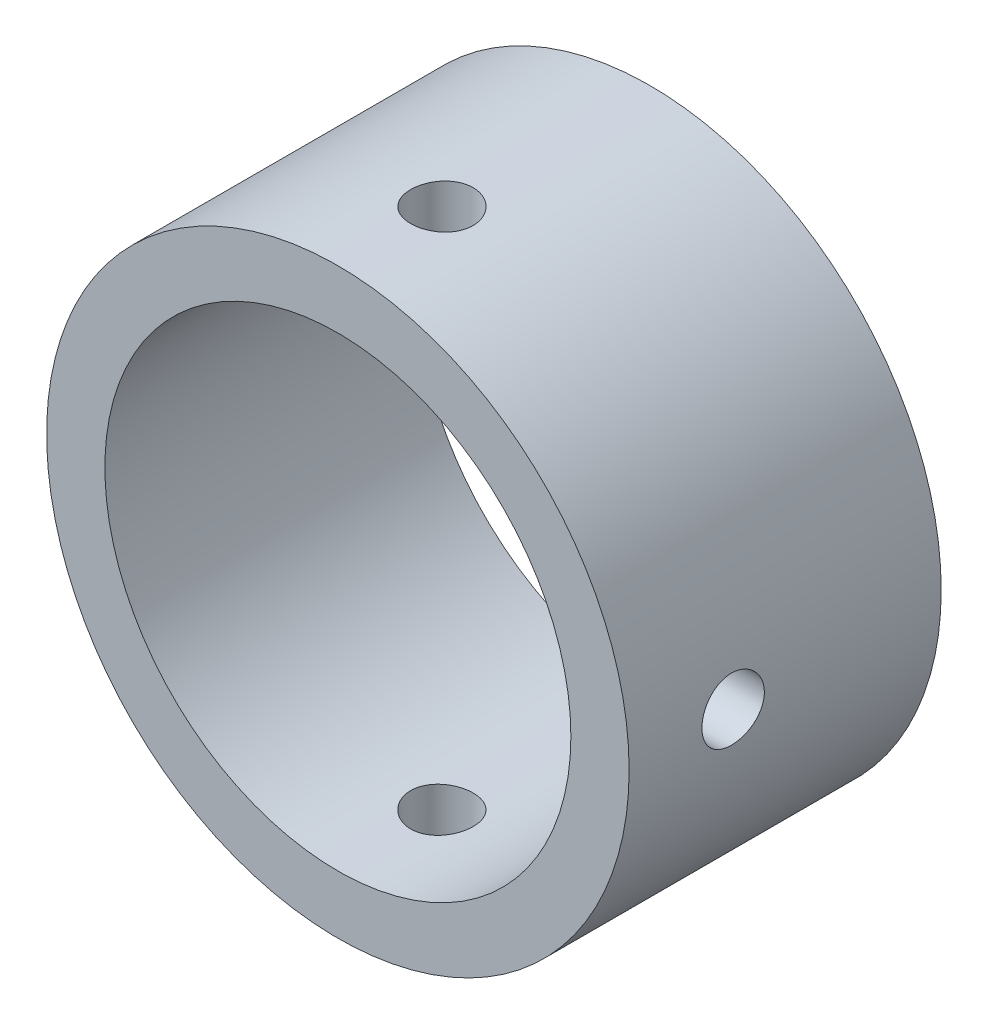
SolidWorks part; units mm, degrees
ref_plane "Front Plane" through (0, 0, 0) normal (0, 0, 1) x (1, 0, 0)
ref_plane "Top Plane" through (0, 0, 0) normal (0, 1, 0) x (1, 0, 0)
ref_plane "Right Plane" through (0, 0, 0) normal (1, 0, 0) x (0, 0, -1)
ref_axis "Z" through (0, 0, 5.75) along (0, 0, -1)
ref_axis "X" through (17.0818, 0, 0) along (-1, 0, 0)
ref_axis "Y" through (0, 15.4, 0) along (0, -1, 0)
sketch "Sketch1" plane through (0, 0, 0) normal (0, 0, 1) x (1, 0, 0)
  circle A0 centre (0, 0) radius 14
  circle A1 centre (0, 0) radius 11.2
  dimension "D1" = 28
  dimension "D2" = 22.4
extrude "Boss-Extrude1" add sketch "Sketch1" against normal blind 10 and the other way blind 5
sketch "Sketch2" plane through (0, 0, 0) normal (0, 1, 0) x (1, 0, 0)
  line L0 (-15.4, 0) -> (15.4, 0) construction
  line L1 (0, -8.25) -> (0, 8.25) construction
  circle A0 centre (0, 0) radius 1.5
  dimension "D1" = 3
extrude "Cut-Extrude1" cut sketch "Sketch2" against normal through all both and the other way through all
sketch "Sketch3" plane through (0, 0, 0) normal (1, 0, 0) x (0, 0, -1)
  circle A0 centre (0, 0) radius 1.5
  dimension "D1" = 3
extrude "Cut-Extrude2" cut sketch "Sketch3" along normal through all
equation "\"EyeDiameter\" = 28"
equation "\"BasePlaneDistance\" = 45"
equation "\"EyeClearance\" = 2"
equation "\"EyeOD\"= \"EyeDiameter\""
equation "\"D1@Sketch1\"=\"EyeOD\""
equation "\"D2@Sketch1\"=\"EyeDiameter\"*0.8"
equation "\"pinHoleDiameter\"= 3"
equation "\"D1@Sketch2\"=\"pinHoleDiameter\""
equation "\"D1@Sketch3\"=\"pinHoleDiameter\""
